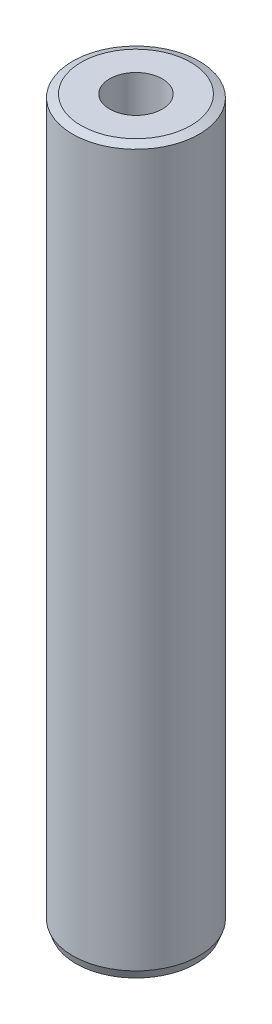
SolidWorks part; units mm, degrees
ref_plane "Front Plane" through (0, 0, 0) normal (0, 0, 1) x (1, 0, 0)
ref_plane "Top Plane" through (0, 0, 0) normal (0, 1, 0) x (1, 0, 0)
ref_plane "Right Plane" through (0, 0, 0) normal (1, 0, 0) x (0, 0, -1)
sketch "Sketch1" plane through (0, 0, 0) normal (0, 1, 0) x (1, 0, 0)
  circle A0 centre (0, 0) radius 52.5
  dimension "SHAFT_OD" = 105
extrude "Boss-Extrude1" add sketch "Sketch1" along normal blind 600
sketch "Sketch2" plane through (0, 0, 0) normal (0, 1, 0) x (1, 0, 0)
  circle A0 centre (0, 0) radius 21.8333
  dimension "BORE_D" = 43.6667
extrude "Cut-Extrude1" cut sketch "Sketch2" along normal through all
chamfer "Chamfer1" distance 2.672 angle 69.11 2 edges at (0, 600, 52.5) (0, 0, 52.5) first distance on face at (0, 600, 52.5) first distance on face at (0, 0, 21.8333)
